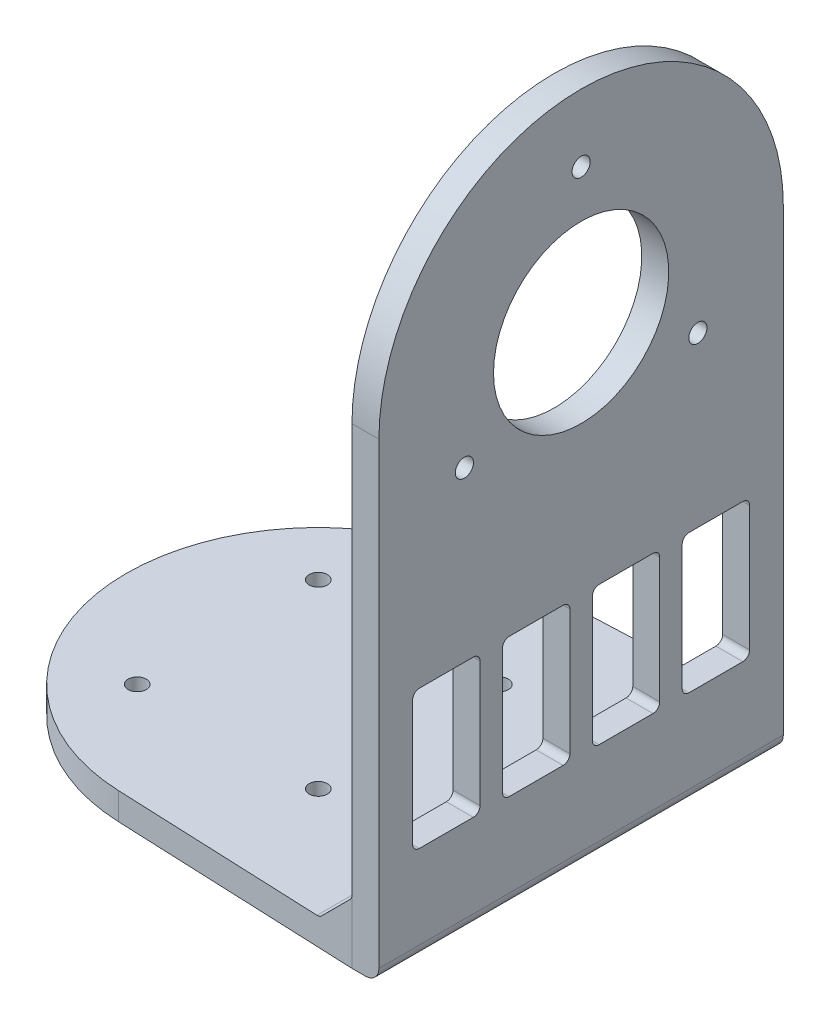
SolidWorks part; units mm, degrees
material "3.1325 (EN-AW 2017A)"
ref_plane "前视基准面" through (0, 0, 0) normal (0, 0, 1) x (1, 0, 0)
ref_plane "上视基准面" through (0, 0, 0) normal (0, 1, 0) x (1, 0, 0)
ref_plane "右视基准面" through (0, 0, 0) normal (1, 0, 0) x (0, 0, -1)
other "Configuration Table"
sketch "草图1" plane through (0, 0, 0) normal (0, 1, 0) x (1, 0, 0)
  line L0 (-1.1998, 28.4747) -> (35, 30)
  line L1 (35, 30) -> (35, -30)
  line L2 (35, -30) -> (-1.1998, -28.4747)
  arc A0 (-1.1998, 28.4747) -> (-1.1998, -28.4747) centre (0, 0) ccw
  point P4 (35, 0)
  dimension "D2" = 28.5
  dimension "D1" = 35
  dimension "D3" = 60
extrude "凸台-拉伸1" add sketch "草图1" along normal blind 4
sketch "草图3" plane through (35, 0, 0) normal (1, 0, 0) x (0, 0, -1)
  line L0 (-30, 0) -> (-30, 70)
  line L1 (-30, 0) -> (30, 0) construction
  line L3 (30, 70) -> (30, 0)
  line L4 (30, 0) -> (-30, 0)
  line L5 (-30, 4) -> (-30, 0) construction
  arc A0 (30, 70) -> (-30, 70) centre (0, 70) ccw
  point P5 (0, 90)
  point P7 (30, 93.9486)
  dimension "D1" = 70
extrude "凸台-拉伸2" add sketch "草图3" along normal blind 4
sketch "草图4" plane through (35, 0, 0) normal (-1, 0, 0) x (0, 0, 1)
  arc A0 (30, 70) -> (-30, 70) centre (0, 70) ccw construction
  arc A1 (30, 70) -> (-30, 70) centre (0, 70) ccw construction
  circle A2 centre (0, 90) radius 1.35
  circle A3 centre (17.3205, 60) radius 1.35
  circle A4 centre (-17.3205, 60) radius 1.35
  circle A5 centre (0, 70) radius 13
  point P12 (0, 70)
  dimension "D3" = 2.7
  dimension "D4" = 26
  dimension "D2" = 20
  dimension "D1" = 3
extrude "切除-拉伸1" cut sketch "草图4" against normal up to surface (4 mm away) up to face at (39, 42.5, 0)
sketch "草图5" plane through (0, 0, 0) normal (0, -1, 0) x (1, 0, 0)
  arc A0 (-1.1998, 28.4747) -> (-1.1998, -28.4747) centre (0, 0) ccw construction
  arc A1 (-1.1998, 28.4747) -> (-1.1998, -28.4747) centre (0, 0) ccw construction
  circle A2 centre (-13.435, 13.435) radius 1.35
  circle A3 centre (13.435, 13.435) radius 1.35
  circle A4 centre (13.435, -13.435) radius 1.35
  circle A5 centre (-13.435, -13.435) radius 1.35
  point P5 (0, 0)
  point P6 (0, 0)
  point P7 (0, 0)
  point P14 (0, 0)
  dimension "D2" = 2.7
  dimension "D3" = 19
  dimension "D1" = 4
extrude "切除-拉伸2" cut sketch "草图5" against normal up to surface (4 mm away) up to face at (10.0751, 4, 0)
sketch "草图6" plane through (0, 0, -30) normal (0, 0, -1) x (-1, 0, 0)
  line L0 (-35, 9) -> (-35, 4)
  line L1 (-35, 4) -> (-35, 70) construction
  line L2 (-35, 4) -> (1.1998, 4) construction
  line L3 (-35, 4) -> (-30, 4)
  line L4 (-30, 4) -> (-35, 9)
  dimension "D1" = 5
  dimension "D2" = 5
extrude "凸台-拉伸3" add sketch "草图6" against normal up to surface (60 mm away) up to face at (16.9001, 2, 29.2374)
fillet "圆角1" radius 1 2 edges at (30, 4, 0) (35, 9, 0)
sketch "草图7" plane through (35, 0, 0) normal (-1, 0, 0) x (0, 0, 1)
  line L1 (-24, 35) -> (-16, 35)
  line L2 (-25, 34) -> (-25, 15.4142)
  line L3 (-24, 14.4142) -> (-16, 14.4142)
  line L4 (-15, 34) -> (-15, 15.4142)
  line L5 (-25, 35) -> (-15, 14.4142) construction
  line L6 (-25, 14.4142) -> (-15, 35) construction
  line L7 (-30, 9.4142) -> (30, 9.4142) construction
  line L8 (-30, 9.4142) -> (-30, 70) construction
  line L68 (-11.6667, 34) -> (-11.6667, 15.4142)
  line L69 (-10.6667, 35) -> (-2.6667, 35)
  line L70 (-1.6667, 34) -> (-1.6667, 15.4142)
  line L71 (-10.6667, 14.4142) -> (-2.6667, 14.4142)
  line L72 (1.6667, 34) -> (1.6667, 15.4142)
  line L73 (2.6667, 35) -> (10.6667, 35)
  line L74 (11.6667, 34) -> (11.6667, 15.4142)
  line L75 (2.6667, 14.4142) -> (10.6667, 14.4142)
  line L76 (15, 34) -> (15, 15.4142)
  line L77 (16, 35) -> (24, 35)
  line L78 (25, 34) -> (25, 15.4142)
  line L79 (16, 14.4142) -> (24, 14.4142)
  line L80 (30, 70) -> (30, 9.4142) construction
  arc A0 (30, 70) -> (-30, 70) centre (0, 70) ccw construction
  arc A1 (30, 70) -> (-30, 70) centre (0, 70) ccw construction
  circle A2 centre (0, 70) radius 30 construction
  arc A3 (-16, 14.4142) -> (-15, 15.4142) centre (-16, 15.4142) ccw
  arc A4 (-25, 15.4142) -> (-24, 14.4142) centre (-24, 15.4142) ccw
  arc A5 (-24, 35) -> (-25, 34) centre (-24, 34) ccw
  arc A6 (-16, 35) -> (-15, 34) centre (-16, 34) cw
  arc A35 (-10.6667, 35) -> (-11.6667, 34) centre (-10.6667, 34) ccw
  arc A36 (-11.6667, 15.4142) -> (-10.6667, 14.4142) centre (-10.6667, 15.4142) ccw
  arc A37 (-2.6667, 35) -> (-1.6667, 34) centre (-2.6667, 34) cw
  arc A38 (-2.6667, 14.4142) -> (-1.6667, 15.4142) centre (-2.6667, 15.4142) ccw
  arc A39 (2.6667, 35) -> (1.6667, 34) centre (2.6667, 34) ccw
  arc A40 (1.6667, 15.4142) -> (2.6667, 14.4142) centre (2.6667, 15.4142) ccw
  arc A41 (10.6667, 35) -> (11.6667, 34) centre (10.6667, 34) cw
  arc A42 (10.6667, 14.4142) -> (11.6667, 15.4142) centre (10.6667, 15.4142) ccw
  arc A43 (16, 35) -> (15, 34) centre (16, 34) ccw
  arc A44 (15, 15.4142) -> (16, 14.4142) centre (16, 15.4142) ccw
  arc A45 (24, 35) -> (25, 34) centre (24, 34) cw
  arc A46 (24, 14.4142) -> (25, 15.4142) centre (24, 15.4142) ccw
  point P4 (-20, 24.7071)
  dimension "D7" = 1
  dimension "D1" = 35
  dimension "D2" = 5
  dimension "D3" = 5
  dimension "D4" = 10
  dimension "D6" = 5
  dimension "D5" = 4
extrude "切除-拉伸3" cut sketch "草图7" against normal up to surface (4 mm away) up to face at (39, 60, -18.6705)
fillet "圆角2" radius 2 1 edges at (39, 0, 0)
